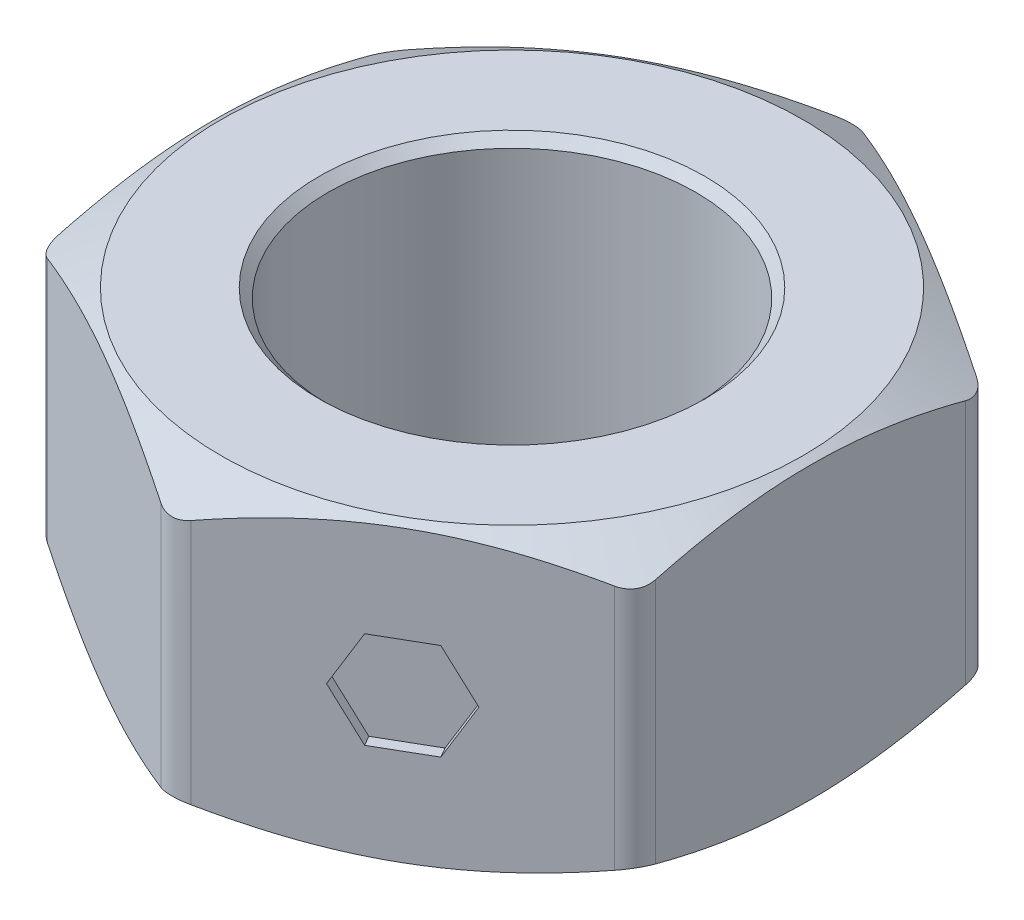
SolidWorks part; units mm, degrees
ref_plane "Front Plane" through (0, 0, 0) normal (0, 0, 1) x (1, 0, 0)
ref_plane "Top Plane" through (0, 0, 0) normal (0, 1, 0) x (1, 0, 0)
ref_plane "Right Plane" through (0, 0, 0) normal (1, 0, 0) x (0, 0, -1)
sketch "Sketch1" plane through (0, 0, 0) normal (0, 0, 1) x (1, 0, 0)
  line L0 (0, -3.25) -> (0, 3.25) construction
  line L1 (6.5, 0) -> (-6.5, 0) construction
  line L2 (4, -3.25) -> (-4, -3.25) construction
  line L3 (4, -3.25) -> (4, -2) construction
  point P4 (0, 0)
  point P8 (0, 0)
  point P11 (0, -3.25)
  dimension "Height" = 6.5
  dimension "Width" = 13
  dimension "Thread Size" = 8
  dimension "Thread Pitch" = 1.25
sketch "Sketch2" plane through (0, 0, 0) normal (0, 1, 0) x (1, 0, 0)
  line L1 (0, 7.5056) -> (-6.5, 3.7528)
  line L2 (-6.5, 3.7528) -> (-6.5, -3.7528)
  line L3 (-6.5, -3.7528) -> (0, -7.5056)
  line L4 (0, -7.5056) -> (6.5, -3.7528)
  line L5 (6.5, -3.7528) -> (6.5, 3.7528)
  line L6 (6.5, 3.7528) -> (0, 7.5056)
  circle A0 centre (0, 0) radius 6.5 construction
  circle A1 centre (0, 0) radius 4
  point P19 (0, -4)
extrude "Boss-Extrude1" add sketch "Sketch2" along normal up to vertex (3.25 mm away) and the other way up to vertex (3.25 mm away) up to point (0, 3.25, 0) other way up to point (0, -3.25, 0)
fillet "Fillet1" radius 0.65 6 edges at (-6.5, 0, -3.7528) (0, 0, -7.5056) (-6.5, 0, 3.7528) (6.5, 0, -3.7528) (6.5, 0, 3.7528) (0, 0, 7.5056)
sketch "Sketch3" plane through (0, 0, 0) normal (1, 0, 0) x (0, 0, -1)
  line L2 (6.3375, -3.25) -> (7.5056, -2.5756)
  line L3 (3.9404, -3.25) -> (7.3179, -3.25) construction
  line L4 (7.5056, 3.25) -> (7.5056, -3.25) construction
  line L5 (7.5056, -2.5756) -> (7.5056, -3.25)
  line L6 (7.5056, -3.25) -> (6.3375, -3.25)
  line L12 (3.9404, 3.25) -> (7.3179, 3.25) construction
  line L16 (4, 3.25) -> (4, 3.05)
  line L17 (4, 3.25) -> (4.2, 3.25)
  line L21 (4, -3.25) -> (4, -3.05)
  line L22 (-3.3775, -3.25) -> (3.3775, -3.25) construction
  line L24 (4.2, -3.25) -> (4, -3.25)
  line L25 (4, -3.05) -> (4.2, -3.25)
  line L26 (4.2, 3.25) -> (4, 3.05)
  line L28 (0, -3.25) -> (0, 3.25) construction
  line L29 (0, -3.25) -> (0, 3.25) construction
  line L33 (6.3375, 3.25) -> (7.5056, 2.5756)
  line L34 (6.3375, 3.25) -> (6.5, 3.25) construction
  line L35 (4, 0) -> (6.5, 0) construction
  line L36 (4, -3.25) -> (4, 3.25) construction
  line L37 (3.9404, -3.25) -> (7.3179, -3.25) construction
  line L38 (6.5, 3.25) -> (6.5, 0) construction
  line L43 (7.5056, 2.5756) -> (7.5056, 3.25)
  line L47 (7.5056, 3.25) -> (6.3375, 3.25)
  point P1 (6.5, 0)
  point P14 (4, 0)
  dimension "D2" = 30
  dimension "D5" = 0.2
  dimension "D1" = 30
  dimension "D3" = 0.1625
revolve "Cut-Revolve2" cut sketch "Sketch3" angle 360 about L0
sketch "Sketch12" plane through (3.25, 0, 5.6292) normal (0.5, 0, 0.866) x (0.866, 0, -0.5)
  line L0 (0, 3.1562) -> (0, 1.0521) construction
  line L1 (0, 1.0521) -> (0, -1.0521) construction
  line L2 (0, -1.0521) -> (0, -3.1562) construction
  line L5 (-1.2148, 0) -> (-0.6074, -1.0521)
  line L6 (-0.6074, -1.0521) -> (0.6074, -1.0521)
  line L7 (0.6074, -1.0521) -> (1.2148, 0)
  line L8 (1.2148, 0) -> (0.6074, 1.0521)
  line L9 (0.6074, 1.0521) -> (-0.6074, 1.0521)
  line L10 (-0.6074, 1.0521) -> (-1.2148, 0)
  circle A0 centre (0, 0) radius 1.0521 construction
  spline S0 degree 3 poles (3.3775, 2.6798) (2.2712, 2.9743) (1.1516, 3.1551) (-0.2743, 3.1565) (-0.5618, 3.1457) (-1.1332, 3.1031) (-1.4172, 3.0713) (-2.2646, 2.9475) (-2.8233, 2.8273) (-3.3775, 2.6798) knots 0 0 0 0 0.5 0.5 0.625 0.625 0.75 0.75 1 1 1 1 construction
  spline S1 degree 3 poles (-3.3775, -2.6798) (-2.2712, -2.9743) (-1.1516, -3.1551) (0.2743, -3.1565) (0.5618, -3.1457) (1.1332, -3.1031) (1.4172, -3.0713) (2.2646, -2.9475) (2.8233, -2.8273) (3.3775, -2.6798) knots 0 0 0 0 0.5 0.5 0.625 0.625 0.75 0.75 1 1 1 1 construction
  point P9 (0, 0)
extrude "Cut-Extrude2" cut sketch "Sketch12" against normal blind 0.25
sketch "Sketch5" plane through (0, 0, 0) normal (0, 1, 0) x (1, 0, 0)
  circle A2 centre (0, 0) radius 4 construction
  point P0 (0, -4)
sketch "Sketch6" [suppressed] plane through (0, 0, 0) normal (0, 0, 1) x (1, 0, 0)
  line L0 (4, 3.25) -> (4, -3.25)
  line L2 (0, -3.25) -> (6.5, -3.25) construction
  line L3 (4, -3.25) -> (0, -3.25)
  line L4 (0, -3.25) -> (0, 3.25)
  line L5 (0, -3.25) -> (0, 3.25) construction
  line L6 (0, 3.25) -> (4, 3.25)
revolve "Revolve2" [suppressed] add sketch "Sketch6" angle 360 about L4
sketch "Sketch7" [suppressed] plane through (0, -3.25, 0) normal (0, -1, 0) x (1, 0, 0)
  circle A2 centre (0, 0) radius 4
  circle A3 centre (0, 0) radius 4
  dimension "D1" = 0
curve "Helix/Spiral1" [suppressed] pitch 1.25 height 7.75 turns 6.2
sketch "Sketch8" [suppressed] plane through (0, 0, 0) normal (0, 0, 1) x (1, 0, 0)
  line L0 (4.1353, -3.1719) -> (3.0528, -3.7969) construction
  line L1 (3.0528, -3.7969) -> (4.1353, -4.4219) construction
  line L2 (4.1353, -4.4219) -> (4.1353, -3.1719) construction
  line L3 (3.1881, -3.7187) -> (3.1881, -3.875)
  line L4 (4, -3.25) -> (4, -4.3437) construction
  line L5 (4, -3.7969) -> (4.1353, -3.7969) construction
  line L6 (3.0528, -3.7969) -> (3.1881, -3.7969) construction
  line L7 (4.0677, -3.7969) -> (4.0677, -4.3828) construction
  line L8 (3.1881, -3.7187) -> (4.1353, -3.1719)
  line L9 (4.1353, -3.1719) -> (4.0677, -4.3828)
  line L10 (3.1881, -3.875) -> (4.0677, -4.3828)
  dimension "D1" = 1.25
  dimension "D2" = 0.1562
sweep "Cut-Sweep1" [suppressed] cut profiles "Sketch8" path "Helix/Spiral1"
sketch "Sketch9" [suppressed] plane through (0, 0, 0) normal (0, 0, 1) x (1, 0, 0)
  line L0 (0, 0.75) -> (0, -3.25)
  line L1 (0, 0.75) -> (0, 0.95)
  line L2 (0, -3.25) -> (4, -3.25)
  line L3 (4, -3.25) -> (4.2, -3.25)
  line L4 (4.2, -3.25) -> (0, 0.95)
  dimension "D1" = 0.2
revolve "Revolve3" [suppressed] add sketch "Sketch9" angle 360 about L0
sketch "Sketch11" [suppressed] plane through (0, 0, 0) normal (0, 0, 1) x (1, 0, 0)
  line L0 (0, 3.25) -> (0, -0.4375)
  line L1 (0, -3.25) -> (0, 3.25) construction
  line L2 (0, -0.4375) -> (4.2, 3.25)
  line L3 (4.2, 3.25) -> (0, 3.25)
  spline S0 degree 2 poles (-1.1661, -2.2381) (-1.7845, -2.1956) (-2.2543, -2.1562) (-3.1881, -2.0781) (-3.1881, -2) (-3.1881, -1.9219) (-2.2543, -1.8437) (-1.3206, -1.7656) (0, -1.6875) (1.3206, -1.6094) (2.2543, -1.5312) (3.1881, -1.4531) (3.1881, -1.375) (3.1881, -1.2969) (2.2543, -1.2187) (1.3206, -1.1406) (0, -1.0625) (-1.3206, -0.9844) (-2.2543, -0.9062) (-3.1881, -0.8281) (-3.1881, -0.75) (-3.1881, -0.6719) (-2.2543, -0.5937) (-1.3206, -0.5156) (0, -0.4375) (1.3206, -0.3594) (2.2543, -0.2812) (3.1881, -0.2031) (3.1881, -0.125) (3.1881, -0.0469) (2.2543, 0.0313) (1.3206, 0.1094) (0, 0.1875) (-1.3206, 0.2656) (-2.2543, 0.3438) (-3.1881, 0.4219) (-3.1881, 0.5) (-3.1881, 0.5781) (-2.2543, 0.6563) (-1.3206, 0.7344) (0, 0.8125) (1.3206, 0.8906) (2.2543, 0.9688) (3.1881, 1.0469) (3.1881, 1.125) (3.1881, 1.2031) (2.2543, 1.2813) (1.3206, 1.3594) (0, 1.4375) (-1.3206, 1.5156) (-2.2543, 1.5938) (-3.1881, 1.6719) (-3.1881, 1.75) (-3.1881, 1.8281) (-2.2543, 1.9063) (-1.3206, 1.9844) (0, 2.0625) (1.3206, 2.1406) (2.2543, 2.2188) (3.1881, 2.2969) (3.1881, 2.375) (3.1881, 2.4531) (2.2543, 2.5313) (1.3206, 2.6094) (0, 2.6875) (-1.3206, 2.7656) (-2.2543, 2.8438) (-3.1881, 2.9219) (-3.1881, 3) (-3.1881, 3.0781) (-2.2543, 3.1563) (-1.7154, 3.2013) (-0.991, 3.25) knots 0.288704 0.288704 0.288704 0.296875 0.296875 0.3125 0.3125 0.328125 0.328125 0.34375 0.34375 0.359375 0.359375 0.375 0.375 0.390625 0.390625 0.40625 0.40625 0.421875 0.421875 0.4375 0.4375 0.453125 0.453125 0.46875 0.46875 0.484375 0.484375 0.5 0.5 0.515625 0.515625 0.53125 0.53125 0.546875 0.546875 0.5625 0.5625 0.578125 0.578125 0.59375 0.59375 0.609375 0.609375 0.625 0.625 0.640625 0.640625 0.65625 0.65625 0.671875 0.671875 0.6875 0.6875 0.703125 0.703125 0.71875 0.71875 0.734375 0.734375 0.75 0.75 0.765625 0.765625 0.78125 0.78125 0.796875 0.796875 0.8125 0.8125 0.828125 0.828125 0.837443 0.837443 0.837443 weights 0.96202 0.960193 1 0.92388 1 0.92388 1 0.92388 1 0.92388 1 0.92388 1 0.92388 1 0.92388 1 0.92388 1 0.92388 1 0.92388 1 0.92388 1 0.92388 1 0.92388 1 0.92388 1 0.92388 1 0.92388 1 0.92388 1 0.92388 1 0.92388 1 0.92388 1 0.92388 1 0.92388 1 0.92388 1 0.92388 1 0.92388 1 0.92388 1 0.92388 1 0.92388 1 0.92388 1 0.92388 1 0.92388 1 0.92388 1 0.92388 1 0.92388 1 0.954607 0.963353 construction
revolve "Revolve4" [suppressed] add sketch "Sketch11" angle 360 about L0
sketch "Sketch10" [suppressed] plane through (0, -3.25, 0) normal (0, -1, 0) x (1, 0, 0)
  circle A0 centre (0, 0) radius 4.2 construction
  circle A1 centre (0, 0) radius 4.2
extrude "Boss-Extrude2" [suppressed] add sketch "Sketch10" against normal up to surface (6.5 mm away) up to face at (6.3375, 3.25, 0)
combine bodies "Combine1" [suppressed] operation type subtract main body 110 bodies to subtract 112
equation "\"D5@Sketch3\"=\"Thread Size@Sketch1\"*.025"
equation "\"D4@Helix/Spiral1\" = \"Thread Pitch@Sketch1\""
equation "\"D3@Helix/Spiral1\"=\"Height@Sketch1\"+\"Thread Pitch@Sketch1\""
equation "\"D1@Sketch8\" = \"Thread Pitch@Sketch1\""
equation "\"D2@Sketch8\" = \"Thread Pitch@Sketch1\" / 8"
equation "\"D1@Sketch9\"=\"Thread Size@Sketch1\" * .025"
equation "\"D1@Fillet1\"=\"Width@Sketch1\" * .05"
equation "\"D3@Sketch3\"=\"Width@Sketch1\"*.0125"
equation "\"D1@Cut-Extrude2\"=((\"Width@Sketch1\"-\"Thread Size@Sketch1\")/2)*.1"
